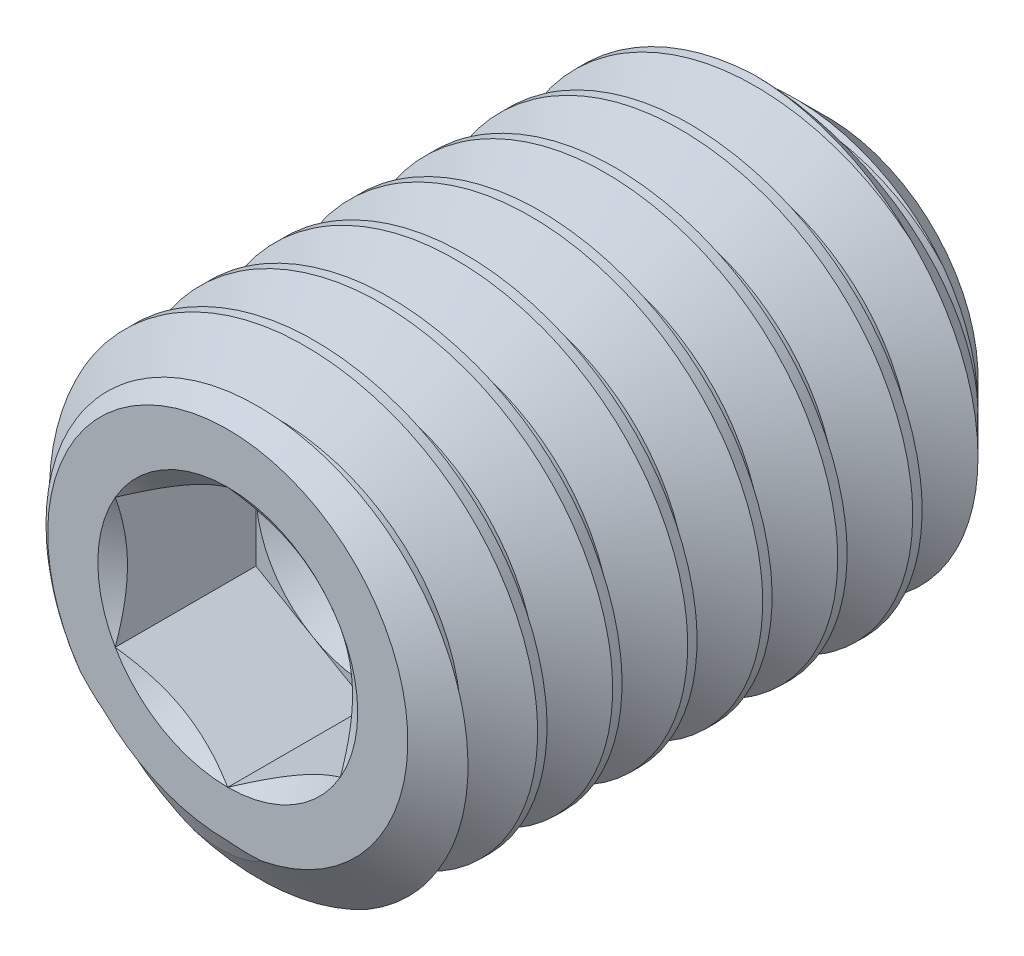
SolidWorks part; units mm, degrees
ref_plane "Front" through (0, 0, 0) normal (0, 0, 1) x (1, 0, 0)
ref_plane "Top" through (0, 0, 0) normal (0, 1, 0) x (1, 0, 0)
ref_plane "Right" through (0, 0, 0) normal (1, 0, 0) x (0, 0, -1)
sketch "Sketch22" plane through (0, 0, 0) normal (1, 0, 0) x (0, 0, -1)
  line L0 (-2, 0) -> (-2, 1.2)
  line L1 (-2, 1.2) -> (-1.7899, 1.5)
  line L2 (-1.7899, 1.5) -> (1.5, 1.5)
  line L3 (1.5, 1.5) -> (2, 1)
  line L4 (-0.145, 1.5) -> (-0.145, -1.5) construction
  line L5 (2, 0) -> (-2, 0)
  line L6 (-2, 1.2) -> (-2, -1.2) construction
  line L7 (2, 0) -> (2, 1)
  point P11 (-0.145, 0)
  dimension "D1" = 2.4
  dimension "Dia" = 3
  dimension "D2" = 0.5
  dimension "Length" = 4
  dimension "D3" = 35
  dimension "D6" = 45
revolve "Revolve1" add sketch "Sketch22" angle 360 about L5
ref_plane "Plane1" through (0, 0, -2) normal (0, 0, 1) x (1, 0, 0)
sketch "Sketch27" plane through (0, 0, -2) normal (0, 0, 1) x (1, 0, 0)
  circle A0 centre (0, 0) radius 1.5 construction
  circle A1 centre (0, 0) radius 1.5
curve "Helix/Spiral1" pitch 0.5 height 4.5 radius 1.5 centre (0, 0, -2) axis (0, 0, 1) start towards (0, 1, 0)
sketch "Sketch28" plane through (0, 0, 0) normal (1, 0, 0) x (0, 0, -1)
  line L0 (2, 1.5) -> (2.4375, 1.5)
  line L1 (2.4375, 1.5) -> (2.25, 1.1752)
  line L2 (2.25, 1.1752) -> (2.1875, 1.1752)
  line L3 (2.1875, 1.1752) -> (2, 1.5)
  line L4 (2.0938, 1.3376) -> (2.3438, 1.3376) construction
  line L6 (-1.7899, 1.5) -> (1.5, 1.5) construction
  dimension "D1" = 0.0625
  dimension "D2" = 0.25
  dimension "D3" = 60
sweep "Cut-Sweep2" cut profiles "Sketch28" path "Helix/Spiral1" align with end faces yes
sketch "Sketch23" plane through (0, 0, 2) normal (0, 0, 1) x (1, 0, 0)
  line L1 (0, 0.866) -> (-0.75, 0.433)
  line L2 (-0.75, 0.433) -> (-0.75, -0.433)
  line L3 (-0.75, -0.433) -> (0, -0.866)
  line L4 (0, -0.866) -> (0.75, -0.433)
  line L5 (0.75, -0.433) -> (0.75, 0.433)
  line L6 (0.75, 0.433) -> (0, 0.866)
  circle A0 centre (0, 0) radius 0.75 construction
  dimension "Hex" = 1.5
extrude "Cut-Extrude10" cut sketch "Sketch23" against normal blind 0.9375
sketch "Sketch24" plane through (0, 0, 2) normal (0, 0, 1) x (1, 0, 0)
  circle A0 centre (0, 0) radius 0.866
extrude "Cut-Extrude11" cut sketch "Sketch24" against normal through all draft 55
sketch "Sketch26" plane through (0, 0, 1.0625) normal (0, 0, 1) x (1, 0, 0)
  circle A0 centre (0, 0) radius 0.75 construction
  circle A1 centre (0, 0) radius 0.75
extrude "Cut-Extrude12" cut sketch "Sketch26" against normal through all draft 60
sketch "Sketch30" plane through (0, 0, 0) normal (1, 0, 0) x (0, 0, -1)
  line L0 (-1.7899, 1.5) -> (1.5, 1.5) construction
  line L1 (-2, 0) -> (-2, 1.2) construction
  line L2 (2, 0) -> (2, 1) construction
  point P0 (-2, 1.5)
  point P1 (2, 1.5)
  point P2 (2, -1.5)
  point P11 (0.75, -1.5)
  dimension "D1" = 1.25
equation "\"D1@Sketch28\" = \"D4@Helix/Spiral1\" * .125"
equation "\"D2@Sketch28\" = \"D4@Helix/Spiral1\" * .5"
equation "\"D3@Helix/Spiral1\" = \"Length@Sketch22\" + \"D4@Helix/Spiral1\""
equation "\"D1@Sketch30\" = \"D4@Helix/Spiral1\" * 2.5"
equation "\"hex Depth@Cut-Extrude10\" = \"Hex@Sketch23\" * .625"
equation "\"D1@Sketch22\" = \"Dia@Sketch22\" * .8"
equation "\"D2@Sketch22\" = \"D4@Helix/Spiral1\""
